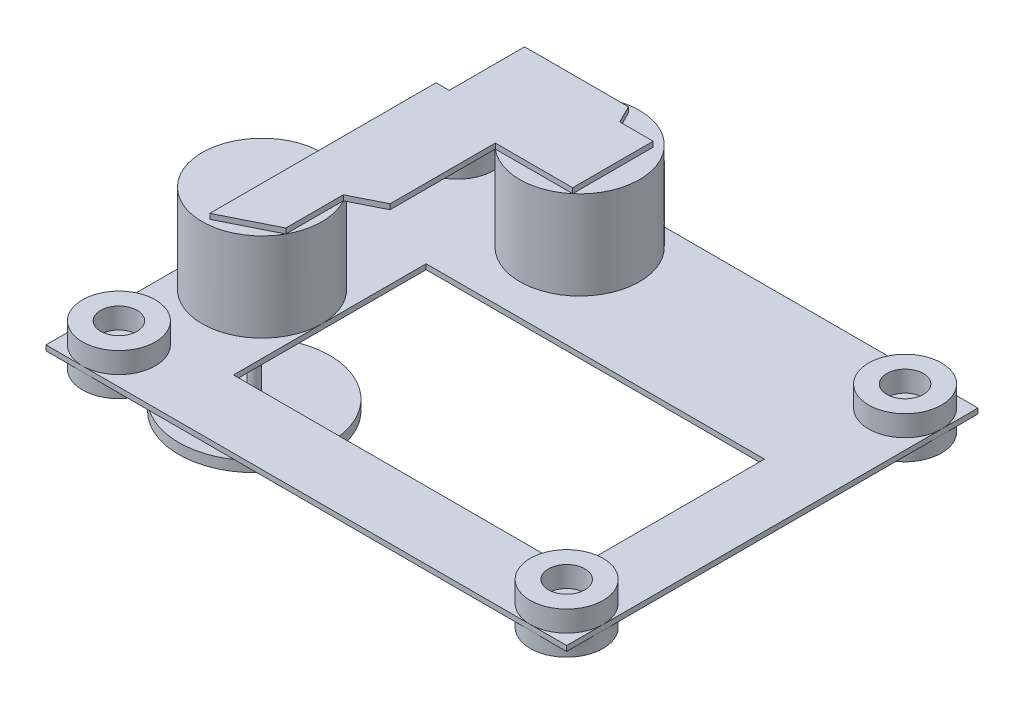
SolidWorks part; units mm, degrees
ref_plane "Plan de face" through (0, 0, 0) normal (0, 0, 1) x (1, 0, 0)
ref_plane "Plan de dessus" through (0, 0, 0) normal (0, 1, 0) x (1, 0, 0)
ref_plane "Plan de droite" through (0, 0, 0) normal (1, 0, 0) x (0, 0, -1)
sketch "Esquisse4" plane through (0, 0, 0) normal (0, 1, 0) x (1, 0, 0)
  line L1 (-50, -39.5) -> (50, -39.5)
  line L2 (-50, -39.5) -> (-50, 39.5)
  line L3 (-50, 39.5) -> (50, 39.5)
  line L4 (50, -39.5) -> (50, 39.5)
  line L5 (-50, -39.5) -> (50, 39.5) construction
  line L6 (-50, 39.5) -> (50, -39.5) construction
  point P0 (0, 0)
  dimension "D1" = 100
  dimension "D2" = 79
extrude "Boss.-Extru.3" add sketch "Esquisse4" against normal blind 1
sketch "Esquisse1" plane through (0, 0, 0) normal (0, 1, 0) x (1, 0, 0)
  line L0 (36, 39.5) -> (36, 25.5) construction
  line L1 (-50, -39.5) -> (50, -39.5)
  line L2 (-50, -39.5) -> (-50, 39.5)
  line L3 (-50, 39.5) -> (50, 39.5)
  line L4 (50, -39.5) -> (50, 39.5)
  line L5 (-50, -39.5) -> (50, 39.5) construction
  line L6 (-50, 39.5) -> (50, -39.5) construction
  line L7 (36, 25.5) -> (50, 25.5) construction
  line L8 (36, 25.5) -> (50, 39.5) construction
  line L9 (-36, 39.5) -> (-36, 25.5) construction
  line L10 (-36, 25.5) -> (-50, 25.5) construction
  line L11 (-36, 25.5) -> (-50, 39.5) construction
  line L12 (-50, -25.5) -> (-36, -25.5) construction
  line L13 (-36, -25.5) -> (-36, -39.5) construction
  line L14 (-36, -25.5) -> (-50, -39.5) construction
  line L15 (50, -25.5) -> (36, -25.5) construction
  line L16 (36, -25.5) -> (36, -39.5) construction
  line L17 (36, -25.5) -> (50, -39.5) construction
  circle A0 centre (43, 32.5) radius 7
  circle A1 centre (-43, 32.5) radius 7
  circle A2 centre (-43, -32.5) radius 7
  circle A3 centre (43, -32.5) radius 7
  circle A4 centre (-43, 32.5) radius 3.5
  circle A5 centre (43, 32.5) radius 3.5
  circle A6 centre (43, -32.5) radius 3.5
  circle A7 centre (-43, -32.5) radius 3.5
  point P0 (0, 0)
  dimension "D4" = 14
  dimension "D5" = 14
  dimension "D12" = 7
  dimension "D13" = 7
  dimension "D14" = 7
  dimension "D15" = 7
  dimension "D1" = 100
  dimension "D2" = 79
  dimension "D3" = 14
  dimension "D6" = 14
  dimension "D7" = 14
  dimension "D8" = 14
  dimension "D9" = 14
  dimension "D10" = 14
  dimension "D11" = 14
extrude "Boss.-Extru.4" add sketch "Esquisse1" against normal blind 4 and the other way blind 4 contours A0 | A1 | A2 | A3 region at (-47.8097, 0, 37.3097) region at (38.1903, 0, 27.6903) region at (-47.8097, 0, -37.3097) region at (38.1903, 0, -27.6903)
sketch "Esquisse6" plane through (0, 0, 0) normal (0, 1, 0) x (1, 0, 0)
  line L0 (-38.5, -9.5) -> (-50, -9.5) construction
  line L1 (-50, 32.5) -> (-50, -32.5) construction
  line L2 (-38.5, -9.5) -> (-38.5, -39.5) construction
  line L3 (-43, -39.5) -> (43, -39.5) construction
  line L4 (-15, 28) -> (-15, 39.5) construction
  line L5 (43, 39.5) -> (-43, 39.5) construction
  line L6 (-15, 28) -> (-50, 28) construction
  circle A0 centre (-38.5, -9.5) radius 11.5
  circle A1 centre (-15, 28) radius 11.5
  dimension "D1" = 23
  dimension "D2" = 23
  dimension "D3" = 11.5
  dimension "D4" = 30
  dimension "D5" = 11.5
  dimension "D6" = 35
extrude "Boss.-Extru.5" add sketch "Esquisse6" along normal blind 17
sketch "Esquisse7" plane through (0, 17, 0) normal (0, 1, 0) x (1, 0, 0)
  line L0 (-38.1438, -19.8875) -> (-28.4142, -15.0251)
  line L1 (-28.4142, -15.0251) -> (-28.4142, -3.9749)
  line L2 (-28.4142, -3.9749) -> (-22.4283, -0.9834)
  line L3 (-22.4283, -0.9834) -> (-22.4283, 19.221)
  line L4 (-22.4283, 19.221) -> (-7.5717, 19.221)
  line L5 (-7.5717, 19.221) -> (-7.5717, 34.6801)
  line L6 (-7.5717, 34.6801) -> (-13.9887, 34.6801)
  line L7 (-13.9887, 34.6801) -> (-15.6674, 38.0391)
  line L8 (-15.6674, 38.0391) -> (-35.6132, 38.0391)
  line L9 (-35.6132, 38.0391) -> (-35.6132, 23.5595)
  line L12 (-38.1438, 23.5595) -> (-38.1438, 0)
  line L13 (-38.1438, 0) -> (-38.1438, -19.8875)
  line L14 (-38.1438, 23.5595) -> (-35.6132, 23.5595)
  circle A0 centre (-38.5, -9.5) radius 11.5 construction
  circle A1 centre (-38.5, -9.5) radius 11.5 construction
  circle A2 centre (-15, 28) radius 11.5 construction
  circle A3 centre (-15, 28) radius 11.5 construction
extrude "Boss.-Extru.6" add sketch "Esquisse7" along normal blind 1
sketch "Esquisse8" plane through (0, 0, 0) normal (0, 1, 0) x (1, 0, 0)
  line L0 (-43, -39.5) -> (43, -39.5) construction
  line L1 (-27, -26.5) -> (38, -26.5)
  line L2 (-27, -26.5) -> (-27, 10.5)
  line L3 (-27, 10.5) -> (38, 10.5)
  line L4 (38, -26.5) -> (38, 10.5)
  line L5 (50, -32.5) -> (50, 32.5) construction
  dimension "D1" = 13
  dimension "D2" = 37
  dimension "D3" = 65
  dimension "D4" = 12
extrude "Enlèv. mat.-Extru.1" cut sketch "Esquisse8" against normal blind 1
sketch "Esquisse9" plane through (0, -1, 0) normal (0, -1, 0) x (1, 0, 0)
  line L1 (-50, -32.5) -> (-50, 32.5) construction
  line L4 (-43, 39.5) -> (43, 39.5) construction
  circle A0 centre (-40, 9.5) radius 1
  dimension "D1" = 2
  dimension "D2" = 30
  dimension "D3" = 10
extrude "Boss.-Extru.7" add sketch "Esquisse9" along normal blind 18
sketch "Esquisse10" plane through (0, -19, 0) normal (0, -1, 0) x (1, 0, 0)
  circle A0 centre (-40, 9.5) radius 14.5
  dimension "D1" = 29
extrude "Boss.-Extru.8" add sketch "Esquisse10" along normal blind 2
sketch "Esquisse11" plane through (0, -21, 0) normal (0, -1, 0) x (-1, 0, 0)
  line L0 (25.5, -9.5) -> (54.5, -9.5) construction
  circle A0 centre (40, -9.5) radius 14.5 construction
  circle A1 centre (40, -9.5) radius 7.5
  dimension "D1" = 15
extrude "Boss.-Extru.9" add sketch "Esquisse11" along normal blind 4
fillet "Congé1" radius 3 1 edges at (-40, -25, 2)
